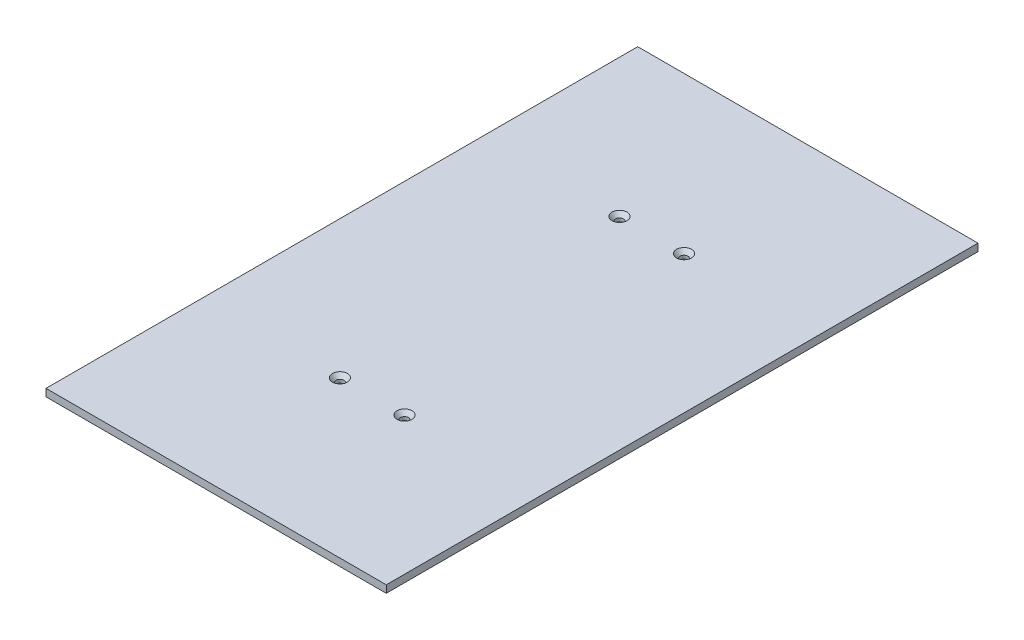
SolidWorks part; units mm, degrees
ref_plane "Front Plane" through (0, 0, 0) normal (0, 0, 1) x (1, 0, 0)
ref_plane "Top Plane" through (0, 0, 0) normal (0, 1, 0) x (1, 0, 0)
ref_plane "Right Plane" through (0, 0, 0) normal (1, 0, 0) x (0, 0, -1)
sketch "Sketch1" plane through (0, 0, 0) normal (0, 1, 0) x (1, 0, 0)
  line L0 (0.9272, 231.0049) -> (293.0272, 231.0049) construction
  line L1 (0.9272, -22.9951) -> (293.0272, -22.9951)
  line L2 (0.9272, -22.9951) -> (0.9272, 485.0049)
  line L3 (0.9272, 485.0049) -> (293.0272, 485.0049)
  line L4 (293.0272, -22.9951) -> (293.0272, 485.0049)
  line L5 (293.0272, 231.0049) -> (146.9772, 485.0049) construction
  line L6 (146.9772, 485.0049) -> (0.9272, 231.0049) construction
  dimension "D1" = 508
  dimension "D2" = 292.1
extrude "Boss-Extrude1" add sketch "Sketch1" along normal blind 6.35 contours L2 L3 L4 L1
sketch "Sketch5" plane through (0, 6.35, 0) normal (0, 1, 0) x (1, 0, 0)
  line L5 (0.9272, 485.0049) -> (293.0272, 485.0049)
  line L6 (0.9272, 485.0049) -> (0.9272, -22.9951)
  line L7 (0.9272, -22.9951) -> (293.0272, -22.9951)
  line L8 (293.0272, 485.0049) -> (293.0272, -22.9951)
  line L9 (146.9772, -22.9951) -> (146.9772, 485.0049) construction
  line L10 (0.9272, 231.0049) -> (293.0272, 231.0049) construction
  circle A0 centre (174.6772, 351.0049) radius 3.5
  circle A1 centre (119.2772, 351.0049) radius 3.5
  circle A2 centre (174.6772, 111.0049) radius 3.5
  circle A3 centre (119.2772, 111.0049) radius 3.5
  point P168 (146.9772, 231.0049)
  dimension "D1" = 7
  dimension "D3" = 120
  dimension "D2" = 27.7
hole_wizard "CSK for 1/4 Flat Head Machine Screw1" positions "3DSketch1" profile "Sketch6" countersink size "1/4" standard "ANSI Inch" end condition through all
sketch3d "3DSketch1"
  point P0 (119.2772, 6.35, -351.0049)
  point P3 (174.6772, 6.35, -351.0049)
  point P6 (174.6772, 6.35, -111.0049)
  point P9 (119.2772, 6.35, -111.0049)
sketch "Sketch6" plane through (119.2772, 6.35, -351.0049) normal (1, 0, 0) x (0, 0, 1)
  line L0 (0, 0) -> (0, 6.35)
  line L1 (0, 6.35) -> (3.3782, 6.35)
  line L2 (3.3782, 6.35) -> (3.3782, 3.5209)
  line L3 (3.3782, 3.5209) -> (6.4389, 0)
  line L5 (6.4389, 0) -> (0, 0)
  line L6 (-3.3782, 3.5209) -> (-6.4389, 0) construction
  line L11 (0, -6.35) -> (0, 107.95) construction
  dimension "Thru Hole Dia." = 6.7564
  dimension "Thru Hole Depth" = 6.35
  dimension "Near C'Sink Dia." = 12.8778
  dimension "Near C'Sink Angle" = 82
